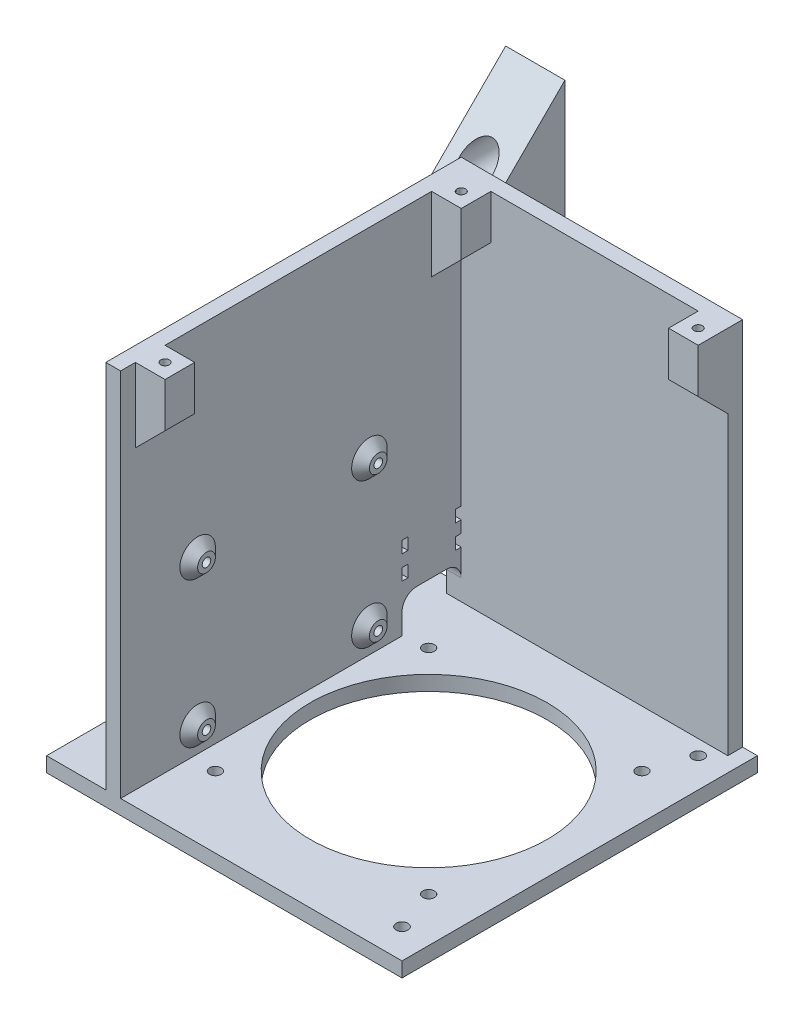
SolidWorks part; units mm, degrees
material "ABS"
ref_plane "Front Plane" through (0, 0, 0) normal (0, 0, 1) x (1, 0, 0)
ref_plane "Top Plane" through (0, 0, 0) normal (0, 1, 0) x (1, 0, 0)
ref_plane "Right Plane" through (0, 0, 0) normal (1, 0, 0) x (0, 0, -1)
sketch "Sketch1" plane through (0, 0, 0) normal (0, 1, 0) x (1, 0, 0)
  line L1 (0, 0) -> (120, 0)
  line L2 (0, 0) -> (0, 120)
  line L3 (0, 120) -> (120, 120)
  line L4 (120, 0) -> (120, 120)
  line L5 (0, 0) -> (120, 120) construction
  line L6 (0, 120) -> (120, 0) construction
  point P4 (60, 60)
  dimension "D1" = 120
  dimension "D2" = 120
extrude "Boss-Extrude1" add sketch "Sketch1" along normal blind 5
sketch "Sketch5" plane through (0, 5, 0) normal (0, 1, 0) x (1, 0, 0)
  line L0 (120, 120) -> (0, 120) construction
  line L1 (20, 120) -> (25, 120)
  line L2 (20, 120) -> (20, 0)
  line L3 (20, 0) -> (25, 0)
  line L4 (25, 120) -> (25, 0)
  line L5 (20, 120) -> (25, 0) construction
  line L6 (20, 0) -> (25, 120) construction
  line L7 (0, 0) -> (120, 0) construction
  line L10 (0, 120) -> (0, 0) construction
  point P4 (22.5, 60)
  dimension "D1" = 5
  dimension "D2" = 20
extrude "Boss-Extrude3" add sketch "Sketch5" along normal blind 125
sketch "Sketch15" plane through (0, 5, 0) normal (0, 1, 0) x (1, 0, 0)
  line L1 (25, 120) -> (115, 120)
  line L2 (25, 120) -> (25, 115)
  line L3 (25, 115) -> (115, 115)
  line L4 (115, 120) -> (115, 115)
  line L5 (25, 120) -> (115, 115) construction
  line L6 (25, 115) -> (115, 120) construction
  point P4 (70, 117.5)
  dimension "D1" = 5
  dimension "D3" = 90
extrude "Boss-Extrude9" add sketch "Sketch15" along normal up to surface (125 mm away) up to face at (22.5, 130, -60)
sketch "Sketch3" plane through (0, 0, 0) normal (0, -1, 0) x (1, 0, 0)
  line L0 (0, -120) -> (0, 0) construction
  line L1 (138, -60) -> (0, -60) construction
  circle A0 centre (69, -60) radius 40
  point P7 (69, -60)
  dimension "D1" = 80
  dimension "D2" = 69
extrude "Cut-Extrude1" cut sketch "Sketch3" against normal blind 15
sketch "Sketch4" plane through (0, 0, 0) normal (0, -1, 0) x (1, 0, 0)
  line L1 (33, -96) -> (105, -96) construction
  line L2 (33, -96) -> (33, -24) construction
  line L3 (33, -24) -> (105, -24) construction
  line L4 (105, -96) -> (105, -24) construction
  line L5 (33, -96) -> (105, -24) construction
  line L6 (33, -24) -> (105, -96) construction
  circle A0 centre (33, -24) radius 1.95
  circle A1 centre (105, -24) radius 1.95
  circle A2 centre (105, -96) radius 1.95
  circle A3 centre (33, -96) radius 1.95
  point P9 (69, -60)
  dimension "D1" = 3.9
  dimension "D2" = 72
extrude "Cut-Extrude2" cut sketch "Sketch4" against normal blind 15
sketch "Sketch6" plane through (25, 0, 0) normal (1, 0, 0) x (0, 0, -1)
  circle A0 centre (26, 62.5) radius 3
  circle A1 centre (84, 62.5) radius 3
  circle A2 centre (84, 13.5) radius 3
  circle A3 centre (26, 13.5) radius 3
extrude "Boss-Extrude4" add sketch "Sketch6" along normal blind 3
sketch "Sketch7" plane through (28, 0, 0) normal (1, 0, 0) x (0, 0, -1)
  circle A0 centre (26, 62.5) radius 1.45
  circle A1 centre (84, 62.5) radius 1.45
  circle A2 centre (84, 13.5) radius 1.45
  circle A3 centre (26, 13.5) radius 1.45
  dimension "D1" = 2.9
extrude "Cut-Extrude3" cut sketch "Sketch7" against normal offset from surface (7 mm away) 1 up to face at (20, 67.5, -60)
sketch "Sketch14" plane through (0, 0, 0) normal (-1, 0, 0) x (0, 0, 1)
  line L0 (-25, 5) -> (-65, 5)
  line L1 (-120, 5) -> (0, 5) construction
  line L2 (-65, 5) -> (-155, 95)
  line L3 (-155, 95) -> (-155, 135)
  line L4 (-155, 135) -> (-25, 5)
  line L5 (-120, 5) -> (0, 5) construction
  dimension "D1" = 40
  dimension "D2" = 40
  dimension "D3" = 45
  dimension "D4" = 130
  dimension "D5" = 25
extrude "Boss-Extrude8" add sketch "Sketch14" against normal up to surface (20 mm away) up to face at (20, 67.5, -60)
sketch "Sketch12" plane through (0, 5, 0) normal (0, 1, 0) x (1, 0, 0)
  line L0 (0, 120) -> (0, 65) construction
  line L1 (20, 120) -> (0, 120) construction
  line L2 (0, 0) -> (20, 0) construction
  circle A0 centre (10, 105) radius 2.65
  circle A1 centre (10, 15) radius 2.65
  dimension "D3" = 5.3
  dimension "D1" = 15
  dimension "D2" = 15
  dimension "D4" = 10
  dimension "D5" = 10
extrude "Cut-Extrude6" cut sketch "Sketch12" against normal through all both and the other way through all
chamfer "Chamfer3" distance 3 angle 45 4 edges at (25, 62.5, -23) (25, 13.5, -23) (25, 13.5, -81) (25, 62.5, -81)
sketch "Sketch17" plane through (0, 130, 0) normal (0, 1, 0) x (1, 0, 0)
  line L0 (25, 0) -> (25, 115) construction
  line L1 (25, 115) -> (35, 115)
  line L2 (25, 115) -> (25, 105)
  line L3 (25, 105) -> (35, 105)
  line L4 (35, 115) -> (35, 105)
  line L5 (25, 115) -> (35, 105) construction
  line L6 (25, 105) -> (35, 115) construction
  line L7 (115, 115) -> (105, 115)
  line L8 (115, 115) -> (115, 105)
  line L9 (115, 105) -> (105, 105)
  line L10 (105, 115) -> (105, 105)
  line L11 (115, 115) -> (105, 105) construction
  line L12 (115, 105) -> (105, 115) construction
  line L13 (25, 5) -> (35, 5)
  line L14 (25, 5) -> (25, 15)
  line L15 (25, 15) -> (35, 15)
  line L16 (35, 5) -> (35, 15)
  line L17 (25, 5) -> (35, 15) construction
  line L18 (25, 15) -> (35, 5) construction
  line L19 (20, 0) -> (25, 0) construction
  point P4 (30, 110)
  point P10 (110, 110)
  point P16 (30, 10)
  dimension "D1" = 10
  dimension "D2" = 10
  dimension "D3" = 10
  dimension "D4" = 10
  dimension "D5" = 10
  dimension "D6" = 10
  dimension "D7" = 5
extrude "Boss-Extrude10" add sketch "Sketch17" against normal blind 15
chamfer "Chamfer4" distance 10 angle 45 3 edges at (110, 115, -115) (25, 115, -10) (25, 115, -110)
sketch "Sketch18" plane through (0, 5, 0) normal (0, 1, 0) x (1, 0, 0)
  line L0 (120, 0) -> (120, 120) construction
  line L1 (25, 0) -> (120, 0) construction
  line L2 (120, 120) -> (115, 120) construction
  circle A0 centre (110, 10) radius 2
  circle A1 centre (110, 110) radius 2
  dimension "D1" = 4
  dimension "D4" = 4
  dimension "D2" = 10
  dimension "D3" = 10
  dimension "D5" = 10
  dimension "D6" = 10
extrude "Cut-Extrude8" cut sketch "Sketch18" against normal blind 15
sketch "Sketch19" plane through (0, 130, 0) normal (0, 1, 0) x (1, 0, 0)
  line L0 (35, 105) -> (35, 115) construction
  line L1 (25, 105) -> (35, 105) construction
  line L2 (25, 0) -> (25, 115) construction
  line L3 (35, 15) -> (25, 15) construction
  line L4 (35, 115) -> (105, 115) construction
  line L5 (115, 105) -> (115, 120) construction
  circle A0 centre (30, 110) radius 1.45
  circle A1 centre (110, 110) radius 1.45
  circle A2 centre (30, 10) radius 1.45
  dimension "D3" = 2.9
  dimension "D1" = 5
  dimension "D2" = 5
  dimension "D4" = 5
  dimension "D5" = 5
  dimension "D6" = 5
  dimension "D7" = 5
extrude "Cut-Extrude9" cut sketch "Sketch19" against normal blind 15
fillet "Fillet4" radius 12 1 edges at (10, 5, -65)
sketch "Sketch20" plane through (0, 0, -155) normal (0, 0, -1) x (-1, 0, 0)
  line L0 (-20, 135) -> (0, 135) construction
  line L1 (0, 135) -> (0, 95) construction
  circle A0 centre (-10, 115) radius 2.65
  dimension "D3" = 5.3
  dimension "D1" = 20
  dimension "D2" = 10
extrude "Cut-Extrude10" cut sketch "Sketch20" against normal through all
ref_plane "Plane2" through (0, 0, -150) normal (0, 0, -1) x (-1, 0, 0)
sketch "Sketch21" plane through (0, 0, -150) normal (0, 0, -1) x (-1, 0, 0)
  circle A0 centre (-10, 115) radius 5.5
  dimension "D1" = 11
extrude "Cut-Extrude11" cut sketch "Sketch21" against normal through all
fillet "Fillet5" radius 5 1 edges at (20, 52.5, -72.5)
sketch "Sketch23" plane through (25, 0, 0) normal (1, 0, 0) x (0, 0, -1)
  line L0 (115, 105) -> (115, 5) construction
  line L1 (115, 5) -> (95, 5)
  line L2 (115, 5) -> (115, 17)
  line L3 (115, 17) -> (95, 17)
  line L4 (95, 5) -> (95, 17)
  line L5 (115, 5) -> (95, 17) construction
  line L6 (115, 17) -> (95, 5) construction
  line L7 (95, 21) -> (97, 21)
  line L8 (95, 21) -> (95, 25)
  line L9 (95, 25) -> (97, 25)
  line L10 (97, 21) -> (97, 25)
  line L11 (95, 21) -> (97, 25) construction
  line L12 (95, 25) -> (97, 21) construction
  line L13 (113, 21) -> (115, 21)
  line L14 (113, 21) -> (113, 25)
  line L15 (113, 25) -> (115, 25)
  line L16 (115, 21) -> (115, 25)
  line L17 (113, 21) -> (115, 25) construction
  line L18 (113, 25) -> (115, 21) construction
  line L19 (113, 29) -> (113, 33)
  line L20 (113, 29) -> (115, 29)
  line L21 (115, 29) -> (115, 33)
  line L22 (113, 33) -> (115, 33)
  line L23 (95, 29) -> (95, 33)
  line L24 (95, 29) -> (97, 29)
  line L25 (97, 29) -> (97, 33)
  line L26 (95, 33) -> (97, 33)
  point P4 (105, 11)
  point P10 (96, 23)
  point P15 (114, 23)
  dimension "D1" = 12
  dimension "D2" = 20
  dimension "D3" = 2
  dimension "D4" = 4
  dimension "D5" = 2
  dimension "D6" = 4
  dimension "D7" = 4
  dimension "D8" = 2
extrude "Cut-Extrude12" cut sketch "Sketch23" against normal blind 10
fillet "Fillet6" radius 5 2 edges at (22.5, 17, -95) (22.5, 17, -115)
fillet "Fillet7" radius 2 4 edges at (20, 23, -113) (20, 23, -97) (20, 31, -97) (20, 31, -113)
